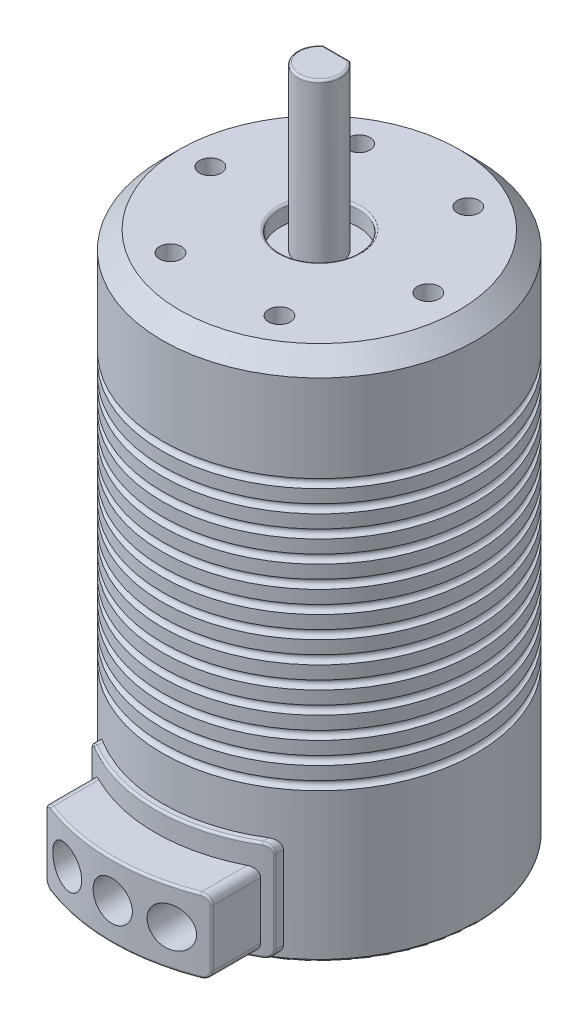
SolidWorks part; units mm, degrees
material "7075-O (SS)"
ref_plane "Front Plane" through (0, 0, 0) normal (0, 0, 1) x (1, 0, 0)
ref_plane "Top Plane" through (0, 0, 0) normal (0, 1, 0) x (1, 0, 0)
ref_plane "Right Plane" through (0, 0, 0) normal (1, 0, 0) x (0, 0, -1)
sketch "Sketch1" plane through (0, 0, 0) normal (0, 0, 1) x (1, 0, 0)
  line L0 (0, 0) -> (0, -77.0212) construction
  line L1 (4.5, 0) -> (18, 0)
  line L2 (4.5, 0) -> (4.5, -60)
  line L3 (4.5, -60) -> (18, -60)
  line L4 (18, 0) -> (18, -60)
  dimension "D1" = 60
  dimension "D2" = 18
  dimension "D3" = 4.5
revolve "Revolve1" add sketch "Sketch1" angle 360 about L0
sketch "Sketch2" plane through (0, 0, 0) normal (0, 0, 1) x (1, 0, 0)
  line L0 (18, -60) -> (18, 0) construction
  line L1 (18, 0) -> (-18, 0) construction
  line L2 (18, -12.5) -> (18, -15) construction
  line L4 (0, 0) -> (0, -70.5259) construction
  circle A0 centre (18, -12.5) radius 0.5
  circle A1 centre (18, -15) radius 0.5
  circle A2 centre (18, -17.5) radius 0.5
  circle A3 centre (18, -20) radius 0.5
  circle A4 centre (18, -22.5) radius 0.5
  circle A5 centre (18, -25) radius 0.5
  circle A6 centre (18, -27.5) radius 0.5
  circle A7 centre (18, -30) radius 0.5
  circle A8 centre (18, -32.5) radius 0.5
  circle A9 centre (18, -35) radius 0.5
  circle A10 centre (18, -37.5) radius 0.5
  circle A11 centre (18, -40) radius 0.5
  circle A12 centre (18, -42.5) radius 0.5
  dimension "D1" = 1
  dimension "D2" = 12.5
  dimension "D4" = 2.5
  dimension "D3" = 13
revolve "Cut-Revolve1" cut sketch "Sketch2" angle 360 about L4
sketch "Sketch3" plane through (0, 0, 0) normal (0, 1, 0) x (1, 0, 0)
  circle A0 centre (0, 0) radius 4.5
  circle A1 centre (0, 0) radius 2.5
  dimension "D1" = 5
  dimension "D2" = 9
extrude "Boss-Extrude1" add sketch "Sketch3" against normal offset from surface (56 mm away) 2 from offset 2 up to face at (0, -60, 18) offset against normal yes
extrude "Boss-Extrude2" add sketch "Sketch3<2>" along normal blind 16.6 and the other way offset from surface 1.3 contours A1 region at (0, 0, 0) other way up to face at (0, -60, 18)
sketch "Sketch3<2>" plane through (0, 0, 0) normal (0, 1, 0) x (1, 0, 0) same geometry as "Sketch3"
sketch "Sketch4" plane through (0, 16.6, 0) normal (0, 1, 0) x (1, 0, 0)
  line L0 (-1.5, 2) -> (1.5, 2)
  arc A0 (-1.5, 2) -> (1.5, 2) centre (0, 0) cw
  circle A1 centre (0, 0) radius 2.5 construction
  dimension "D1" = 2
extrude "Cut-Extrude1" cut sketch "Sketch4" against normal blind 15
chamfer "Chamfer1" distance 2 angle 45 1 edges at (0, 0, 18)
sketch "Sketch5" plane through (0, -60, 0) normal (0, -1, 0) x (1, 0, 0)
  line L0 (-10.5, 15.5946) -> (-10.5, 14.6202)
  line L1 (-10.5, 14.6202) -> (10.5, 14.6202)
  line L2 (10.5, 14.6202) -> (10.5, 15.5946)
  line L3 (-9.5, 21.8218) -> (-9.5, 15.2889)
  line L4 (-9.5, 15.2889) -> (9.5, 15.2889)
  line L5 (9.5, 15.2889) -> (9.5, 21.8218)
  circle A0 centre (0, 0) radius 18.8
  circle A1 centre (0, 0) radius 23.8
  circle A2 centre (0, 0) radius 18 construction
  circle M5 centre (0, 0) radius 18
  dimension "D1" = 37.6
  dimension "D2" = 47.6
  dimension "D3" = 21
  dimension "D4" = 19
extrude "Boss-Extrude3" add sketch "Sketch5" against normal blind 11.5 from offset 0.5 contours L3 A0 L0 M5 | L5 A0 L3 M5 | L2 A0 L5 M5 region at (-10.0035, -60, 15.4371) region at (0, -60, 18.6068) region at (10.0035, -60, 15.4371) offset against normal yes
extrude "Boss-Extrude4" add sketch "Sketch5<4>" against normal blind 8.5 from offset 1 contours L5 A1 L3 A0 region at (0, -60, 20.5365) offset against normal yes
sketch "Sketch5<4>" plane through (0, -60, 0) normal (0, -1, 0) x (1, 0, 0) same geometry as "Sketch5"
ref_plane "Plane1" through (0, 0, 23.8) normal (0, 0, 1) x (1, 0, 0)
sketch "Sketch6" plane through (0, 0, 23.8) normal (0, 0, 1) x (1, 0, 0)
  line L1 (-9.5, -59) -> (9.5, -59) construction
  line L2 (9.5, -50.5) -> (9.5, -59) construction
  circle A0 centre (0, -54.75) radius 2.25
  circle A1 centre (6, -54.75) radius 2.25
  circle A2 centre (-6, -54.75) radius 2.25
  dimension "D1" = 4.5
  dimension "D2" = 4.5
  dimension "D3" = 4.5
  dimension "D4" = 6
  dimension "D5" = 6
  dimension "D6" = 4.25
  dimension "D7" = 9.5
extrude "Cut-Extrude2" cut sketch "Sketch6" against normal blind 12.5
fillet "Fillet1" radius 1 8 edges at (10.5, -59.5, 15.1074) (10.5, -48, 15.1074) (9.5, -50.5, 19.0225) (9.5, -59, 19.0225) (-10.5, -59.5, 15.1074) (-10.5, -48, 15.1074) (-9.5, -50.5, 19.0225) (-9.5, -59, 19.0225)
fillet "Fillet2" radius 0.25 21 edges at (9.162, -58.7495, 21.9658) (9.5, -54.75, 21.8218) (9.3096, -50.913, 21.9037) (0, -50.5, 23.8) (-9.162, -50.7505, 21.9658) (-9.5, -54.75, 21.8218) (-9.3096, -58.587, 21.9037) (10.2488, -59.1628, 15.7608) (10.5, -53.75, 15.5946) (10.3366, -48.4522, 15.7033) (0, -48, 18.8) (-10.2488, -48.3372, 15.7608) (-10.5, -53.75, 15.5946) (-10.3366, -59.0478, 15.7033) (0, -59, 23.8) (0, -59.5, 18.8) (0, 16.6, -2) (0, 16.6, 2.5) (0, 0, 4.5) (0, -60, 18) (0, -60, 4.5)
sketch "Sketch7" plane through (0, 0, 0) normal (0, 1, 0) x (1, 0, 0)
  line L0 (-6.25, 10.8253) -> (0, 0) construction
  line L1 (0, 0) -> (0, 23.9957) construction
  circle A0 centre (-6.25, 10.8253) radius 1.25
  circle A1 centre (6.25, 10.8253) radius 1.25
  circle A2 centre (12.5, 0) radius 1.25
  circle A3 centre (6.25, -10.8253) radius 1.25
  circle A4 centre (-6.25, -10.8253) radius 1.25
  circle A5 centre (-12.5, 0) radius 1.25
  point P15 (0, 0)
  dimension "D1" = 2.5
  dimension "D2" = 12.5
  dimension "D4" = 30
  dimension "D3" = 6
extrude "Cut-Extrude3" cut sketch "Sketch7" against normal blind 6
